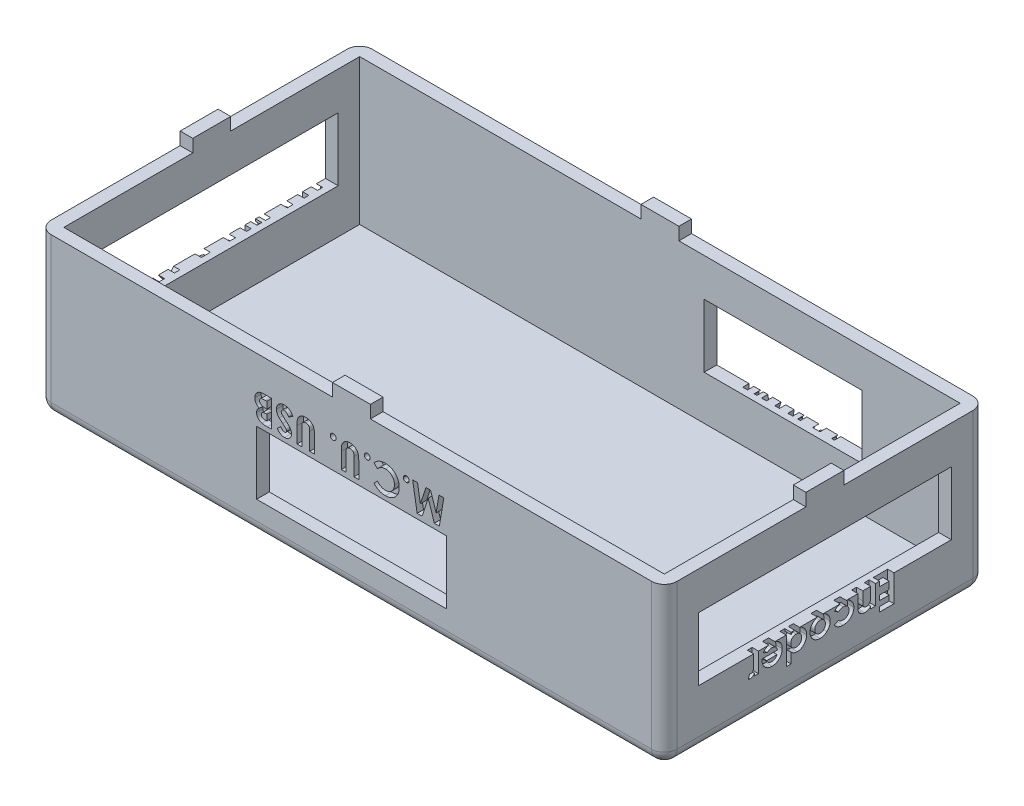
SolidWorks part; units mm, degrees
ref_plane "Front Plane" through (0, 0, 0) normal (0, 0, 1) x (1, 0, 0)
ref_plane "Top Plane" through (0, 0, 0) normal (0, 1, 0) x (1, 0, 0)
ref_plane "Right Plane" through (0, 0, 0) normal (1, 0, 0) x (0, 0, -1)
sketch "Sketch1" plane through (0, 0, 0) normal (0, 1, 0) x (1, 0, 0)
  line L1 (-49.5, 25.4) -> (49.5, 25.4)
  line L2 (-49.5, 25.4) -> (-49.5, -25.4)
  line L3 (-49.5, -25.4) -> (49.5, -25.4)
  line L4 (49.5, 25.4) -> (49.5, -25.4)
  line L5 (-49.5, 25.4) -> (49.5, -25.4) construction
  line L6 (-49.5, -25.4) -> (49.5, 25.4) construction
  point P0 (0, 0)
  dimension "D1" = 50.8
  dimension "D2" = 99
extrude "Boss-Extrude1" add sketch "Sketch1" along normal blind 25
sketch "Sketch2" plane through (0, 25, 0) normal (0, 1, 0) x (1, 0, 0)
  line L0 (-49.5, 25.4) -> (-49.5, -25.4) construction
  line L1 (-47.5, 23.4) -> (47.5, 23.4)
  line L2 (-47.5, 23.4) -> (-47.5, -23.4)
  line L3 (-47.5, -23.4) -> (47.5, -23.4)
  line L4 (47.5, 23.4) -> (47.5, -23.4)
  line L5 (-47.5, 23.4) -> (47.5, -23.4) construction
  line L6 (-47.5, -23.4) -> (47.5, 23.4) construction
  line L8 (-49.5, -25.4) -> (49.5, -25.4) construction
  point P0 (0, 0)
  dimension "D1" = 2
  dimension "D2" = 2
extrude "Cut-Extrude1" cut sketch "Sketch2" against normal blind 23
fillet "Fillet1" radius 2 8 edges at (49.5, 0, 0) (49.5, 12.5, -25.4) (0, 0, -25.4) (-49.5, 12.5, -25.4) (-49.5, 0, 0) (-49.5, 12.5, 25.4) (0, 0, 25.4) (49.5, 12.5, 25.4)
sketch "Sketch3" plane through (0, 0, -25.4) normal (0, 0, -1) x (-1, 0, 0)
  line L0 (-47.5, 25) -> (47.5, 25) construction
  line L1 (-32, 19) -> (-7, 19)
  line L2 (-32, 19) -> (-32, 9)
  line L3 (-32, 9) -> (-7, 9)
  line L4 (-7, 19) -> (-7, 9)
  line L5 (-32, 19) -> (-7, 9) construction
  line L6 (-32, 9) -> (-7, 19) construction
  line L8 (-49.5, 2) -> (-49.5, 25) construction
  point P0 (-19.5, 14)
  dimension "D1" = 11
  dimension "D2" = 30
  dimension "D3" = 10
  dimension "D4" = 25
sketch "Sketch4" plane through (49.5, 0, 0) normal (1, 0, 0) x (0, 0, -1)
  line L0 (-23.4, 25) -> (23.4, 25) construction
  line L1 (20, 9) -> (-20, 9)
  line L2 (20, 9) -> (20, 19)
  line L3 (20, 19) -> (-20, 19)
  line L4 (-20, 9) -> (-20, 19)
  line L5 (20, 9) -> (-20, 19) construction
  line L6 (20, 19) -> (-20, 9) construction
  line L7 (-25.4, 2) -> (-25.4, 25) construction
  line L8 (25.4, 25) -> (25.4, 2) construction
  point P0 (0, 14)
  dimension "D1" = 11
  dimension "D2" = 25.4
  dimension "D3" = 25.4
  dimension "D4" = 10
  dimension "D5" = 40
sketch "Sketch5" plane through (0, 0, 25.4) normal (0, 0, 1) x (1, 0, 0)
  line L0 (-47.5, 25) -> (47.5, 25) construction
  line L1 (15, 5) -> (-15, 5)
  line L2 (15, 5) -> (15, 15)
  line L3 (15, 15) -> (-15, 15)
  line L4 (-15, 5) -> (-15, 15)
  line L5 (15, 5) -> (-15, 15) construction
  line L6 (15, 15) -> (-15, 5) construction
  line L7 (-49.5, 2) -> (-49.5, 25) construction
  line L8 (49.5, 25) -> (49.5, 2) construction
  line L9 (47.5, 0) -> (-47.5, 0) construction
  point P0 (0, 10)
  dimension "D1" = 15
  dimension "D2" = 49.5
  dimension "D3" = 49.5
  dimension "D4" = 10
  dimension "D5" = 30
  dimension "D6" = 10
sketch "Sketch6" plane through (-49.5, 0, 0) normal (-1, 0, 0) x (0, 0, 1)
  line L0 (-23.4, 25) -> (23.4, 25) construction
  line L1 (20, 9) -> (-20, 9)
  line L2 (20, 9) -> (20, 19)
  line L3 (20, 19) -> (-20, 19)
  line L4 (-20, 9) -> (-20, 19)
  line L5 (20, 9) -> (-20, 19) construction
  line L6 (20, 19) -> (-20, 9) construction
  point P0 (0, 14)
  dimension "D1" = 11
  dimension "D2" = 10
  dimension "D3" = 40
extrude "Cut-Extrude2" cut sketch "Sketch3" against normal blind 2
extrude "Cut-Extrude3" cut sketch "Sketch6" against normal blind 2
extrude "Cut-Extrude4" cut sketch "Sketch5" against normal blind 2
extrude "Cut-Extrude5" cut sketch "Sketch4" against normal blind 2
sketch "Sketch7" plane through (49.5, 0, 0) normal (1, 0, 0) x (0, 0, -1)
  text T0 "<b>Encoder</b>" font "Century Gothic" height in points 16
sketch "Sketch8" plane through (0, 0, -25.4) normal (0, 0, -1) x (-1, 0, 0)
  text T0 "<b>I.M.U.</b>" font "Century Gothic" height in points 16
sketch "Sketch9" plane through (0, 0, 25.4) normal (0, 0, 1) x (1, 0, 0)
  line L0 (14.7271, 20) -> (-15, 20) construction
  line L1 (-47.5, 25) -> (47.5, 25) construction
  text T0 "<b>M.C.U. USB</b>" font "Century Gothic" height in points 16
  dimension "D1" = 5
sketch "Sketch10" plane through (-49.5, 0, 0) normal (-1, 0, 0) x (0, 0, 1)
  text T0 "<b>Xbox Outputs</b>" font "Century Gothic" height in points 16
sketch "Sketch11" plane through (0, 0, 0) normal (0, -1, 0) x (1, 0, 0)
  line L0 (-47.5, 0) -> (47.5, 0) construction
  line L1 (-47.5, 23.4) -> (-47.5, -23.4) construction
  line L2 (47.5, -23.4) -> (47.5, 23.4) construction
  line L4 (-47.5, 13.4) -> (47.5, 13.4) construction
  line L5 (47.5, 23.4) -> (-47.5, 23.4) construction
  text T0 "<b>~~~~~~~~~~~~</b>\r\n<b>Arm Cycle </b>\r\n<b>Controller</b>\r\n~~~~~~~~~~~~" font "Century Gothic" height in points 24
  dimension "D1" = 10
extrude "Cut-Extrude10" cut sketch "Sketch11" against normal blind 1
sketch "Sketch12" plane through (0, 0, -25.4) normal (0, 0, -1) x (-1, 0, 0)
  line L0 (-3, 25) -> (3, 25)
  line L1 (-47.5, 25) -> (47.5, 25) construction
  line L2 (3, 25) -> (3, 27)
  line L3 (3, 27) -> (-3, 27)
  line L4 (-3, 27) -> (-3, 25)
  point P5 (0, 25)
extrude "Boss-Extrude2" add sketch "Sketch12" against normal blind 2
sketch "Sketch13" plane through (49.5, 0, 0) normal (1, 0, 0) x (0, 0, -1)
  line L0 (-3, 25) -> (3, 25)
  line L1 (-23.4, 25) -> (23.4, 25) construction
  line L2 (3, 25) -> (3, 27)
  line L3 (3, 27) -> (-3, 27)
  line L4 (-3, 27) -> (-3, 25)
  point P5 (0, 25)
extrude "Boss-Extrude3" add sketch "Sketch13" against normal blind 2
mirror "Mirror1" about plane through (0, 0, 0) normal (0, 0, 1) of "Boss-Extrude2"
mirror "Mirror2" about plane through (0, 0, 0) normal (1, 0, 0) of "Boss-Extrude3"
extrude "Cut-Extrude11" cut sketch "Sketch7" against normal blind 1
extrude "Cut-Extrude12" cut sketch "Sketch10" against normal blind 1
extrude "Cut-Extrude13" cut sketch "Sketch9" against normal blind 1
extrude "Cut-Extrude14" cut sketch "Sketch8" against normal blind 1
